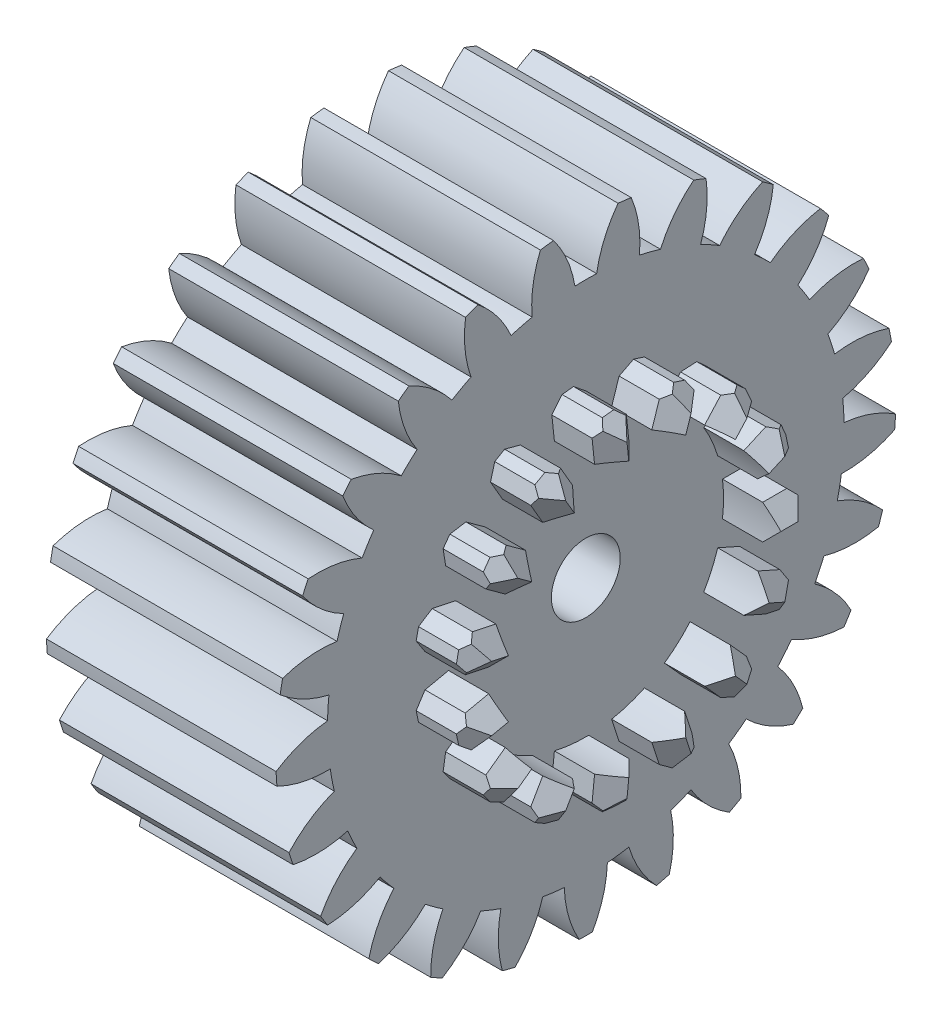
SolidWorks part; units mm, degrees
ref_plane "Plane1" through (0, 0, 0) normal (0, 0, 1) x (1, 0, 0)
ref_plane "Plane2" through (0, 0, 0) normal (0, 1, 0) x (1, 0, 0)
ref_plane "Plane3" through (0, 0, 0) normal (1, 0, 0) x (0, 0, -1)
sketch "HoldingSke" plane through (0, 0, 0) normal (0, 1, 0) x (1, 0, 0)
  line L0 (0, 0) -> (0.4532, -0.2113)
  line L1 (-15, 0) -> (100, 0) construction
  line L2 (0, 0) -> (-2.1039, 2.3779)
  line L3 (0, 0) -> (-11.863, 4.5341)
  line L4 (0, 0) -> (7.8269, 3.6497)
  line L5 (0, 0) -> (-46.8476, -17.4728)
  line L6 (0, 0) -> (-16.5793, -11.1861)
  line L7 (-2.1039, 2.3779) -> (8.6586, 51.2059)
  line L8 (-76.2, 54.61) -> (-75.2, 54.61)
  line L9 (-71.009, 38.7566) -> (-53.1078, 45.2721)
  line L10 (-76.2, 71.12) -> (104.1128, 71.12)
  line L11 (0, 0) -> (-20, 0)
  line L12 (-76.2, 101.6) -> (-76.133, 101.6)
  line L13 (24.9733, 27.94) -> (52.9518, 28.4284)
  line L14 (24.9733, 27.94) -> (24.9743, 27.94)
  line L15 (24.9733, 27.94) -> (100.4006, 29.5858)
  line L16 (-63.627, -2) -> (-12.827, -2)
  circle A0 centre (0, 0) radius 3
  circle A1 centre (0, 0) radius 22.499
  circle A2 centre (0, 0) radius 37.5
  circle A3 centre (0, 0) radius 3
  dimension "Num_teeth" = 25
  dimension "Pitch_radius" = 180.3128
  dimension "Width" = 20
  dimension "Thickness" = 20
sketch "BasProSke" plane through (0, 0, 0) normal (0, 1, 0) x (1, 0, 0)
  line L0 (-10, 0) -> (60, 0) construction
  line L1 (0, 0) -> (0, 27)
  line L2 (0, 0) -> (20, 0)
  line L3 (20, 0) -> (20, 27)
  line L4 (20, 27) -> (0, 27)
  dimension "Thickness" = 20
  dimension "Diameter" = 54
revolve "Base-Revolve" add sketch "BasProSke" angle 360 about L0
sketch "TooCutSke" plane through (0, 0, 0) normal (1, 0, 0) x (0, 0, -1)
  line L1 (0, 0) -> (0, 107) construction
  line L2 (0, 0) -> (-1.687, 24.943) construction
  line L3 (0, 0) -> (-6.2561, 49.5219) construction
  line L4 (-1.687, 24.943) -> (-3.128, 24.761) construction
  arc A0 (0.9462, 22.4791) -> (-0.9462, 22.4791) centre (0, 0) ccw
  arc A1 (2.8295, 26.8769) -> (-2.8295, 26.8769) centre (0, 0) ccw
  circle A2 centre (0, 0) radius 25 construction
  circle A3 centre (0, 0) radius 23.4923 construction
  arc A4 (-0.9462, 22.4791) -> (-2.8295, 26.8769) centre (-10.8135, 20.8556) ccw
  arc A5 (2.8295, 26.8769) -> (0.9462, 22.4791) centre (10.8135, 20.8556) ccw
extrude "ToothCut" cut sketch "TooCutSke" along normal through all
fillet "Breaks" [suppressed] radius 0.04 tangent propagation no
fillet "RootFillets" [suppressed] radius 0.501
pattern_circular "TeethCuts" count 25 every 14.4 about axis through (-10, 0, 0) along (1, 0, 0) of "ToothCut", "RootFillets", "Breaks"
sketch "HubNeaOneSke" plane through (0, 0, 0) normal (-1, 0, 0) x (0, 0, 1)
  circle A0 centre (0, 0) radius 22.499
  dimension "Diameter" = 44.998
extrude "HubNearOne" [suppressed] add sketch "HubNeaOneSke" along normal blind 30.0001
sketch "HubNeaBotSke" plane through (0, 0, 0) normal (-1, 0, 0) x (0, 0, 1)
  circle A0 centre (0, 0) radius 22.499
  dimension "Diameter" = 44.998
extrude "HubNearBoth" [suppressed] add sketch "HubNeaBotSke" along normal blind 15
ref_plane "FarPln" through (20, 0, 0) normal (1, 0, 0) x (0, 0, -1)
sketch "HubFarSke" plane through (20, 0, 0) normal (1, 0, 0) x (0, 0, -1)
  circle A0 centre (0, 0) radius 22.499
  dimension "Diameter" = 44.998
extrude "HubFar" [suppressed] add sketch "HubFarSke" along normal blind 15
sketch "BorSke" plane through (0, 0, 0) normal (1, 0, 0) x (0, 0, -1)
  circle A0 centre (0, 0) radius 3
  dimension "Diameter" = 6
extrude "Bore" cut sketch "BorSke" along normal mid plane 100.0001
sketch "KeySke" plane through (0, 0, 0) normal (1, 0, 0) x (0, 0, -1)
  line L0 (-1, 0) -> (-1, 4)
  line L1 (-1, 4) -> (1, 4)
  line L2 (1, 4) -> (1, 0)
  line L3 (0, 0) -> (0, 34) construction
  line L4 (-1, 0) -> (1, 0)
  dimension "Width" = 2
extrude "Keyway" [suppressed] cut sketch "KeySke" along normal mid plane 100.0001
pattern_circular "Keyway2" [suppressed] count 2 every 90 about axis through (-10, 0, 0) along (1, 0, 0) reverse direction yes
sketch "Sketch3" plane through (20, 0, 0) normal (1, 0, 0) x (0, 0, -1)
  line L0 (0, 0) -> (12, 0) construction
  line L1 (12, 0) -> (15, 0) construction
  line L2 (15, 0.5) -> (15, -0.5)
  line L3 (14, -1.5) -> (11.9059, -1.5)
  line L4 (14, 1.5) -> (11.9059, 1.5)
  line L5 (11.9059, 1.5) -> (11.9059, -1.5)
  line L6 (15, -0.5) -> (14, -1.5)
  line L7 (15, 0.5) -> (14, 1.5)
  line L8 (11.4867, -3.4722) -> (10.2665, -6.2129)
  line L9 (12.1795, -7.0646) -> (10.2665, -6.2129)
  line L10 (13.4998, -6.5578) -> (12.1795, -7.0646)
  line L11 (13.9066, -5.6443) -> (13.4998, -6.5578)
  line L12 (13.9066, -5.6443) -> (13.3997, -4.324)
  line L13 (13.3997, -4.324) -> (11.4867, -3.4722)
  line L14 (9.0813, -7.8441) -> (6.8519, -9.8515)
  line L15 (8.2531, -11.4077) -> (6.8519, -9.8515)
  line L16 (9.6654, -11.4817) -> (8.2531, -11.4077)
  line L17 (10.4085, -10.8126) -> (9.6654, -11.4817)
  line L18 (10.4085, -10.8126) -> (10.4825, -9.4003)
  line L19 (10.4825, -9.4003) -> (9.0813, -7.8441)
  line L20 (5.1057, -10.8596) -> (2.2525, -11.7867)
  line L21 (2.8997, -13.7783) -> (2.2525, -11.7867)
  line L22 (4.1597, -14.4204) -> (2.8997, -13.7783)
  line L23 (5.1108, -14.1113) -> (4.1597, -14.4204)
  line L24 (5.1108, -14.1113) -> (5.7528, -12.8513)
  line L25 (5.7528, -12.8513) -> (5.1057, -10.8596)
  line L26 (0.2473, -11.9975) -> (-2.7363, -11.6839)
  line L27 (-2.9552, -13.7665) -> (-2.7363, -11.6839)
  line L28 (-2.0652, -14.8656) -> (-2.9552, -13.7665)
  line L29 (-1.0707, -14.9701) -> (-2.0652, -14.8656)
  line L30 (-1.0707, -14.9701) -> (0.0284, -14.0801)
  line L31 (0.0284, -14.0801) -> (0.2473, -11.9975)
  line L32 (-4.6539, -11.0608) -> (-7.252, -9.5608)
  line L33 (-8.299, -11.3744) -> (-7.252, -9.5608)
  line L34 (-7.933, -12.7404) -> (-8.299, -11.3744)
  line L35 (-7.067, -13.2404) -> (-7.933, -12.7404)
  line L36 (-7.067, -13.2404) -> (-5.701, -12.8744)
  line L37 (-5.701, -12.8744) -> (-4.6539, -11.0608)
  line L38 (-8.7504, -8.2116) -> (-10.5137, -5.7846)
  line L39 (-12.2079, -7.0155) -> (-10.5137, -5.7846)
  line L40 (-12.4291, -8.4123) -> (-12.2079, -7.0155)
  line L41 (-11.8414, -9.2213) -> (-12.4291, -8.4123)
  line L42 (-11.8414, -9.2213) -> (-10.4446, -9.4425)
  line L43 (-10.4446, -9.4425) -> (-8.7504, -8.2116)
  line L44 (-11.3338, -3.9426) -> (-11.9576, -1.0082)
  line L45 (-14.0059, -1.4435) -> (-11.9576, -1.0082)
  line L46 (-14.7762, -2.6296) -> (-14.0059, -1.4435)
  line L47 (-14.5683, -3.6077) -> (-14.7762, -2.6296)
  line L48 (-14.5683, -3.6077) -> (-13.3822, -4.378)
  line L49 (-13.3822, -4.378) -> (-11.3338, -3.9426)
  line L50 (-11.9576, 1.0082) -> (-11.3338, 3.9426)
  line L51 (-13.3822, 4.378) -> (-11.3338, 3.9426)
  line L52 (-14.5683, 3.6077) -> (-13.3822, 4.378)
  line L53 (-14.7762, 2.6296) -> (-14.5683, 3.6077)
  line L54 (-14.7762, 2.6296) -> (-14.0059, 1.4435)
  line L55 (-14.0059, 1.4435) -> (-11.9576, 1.0082)
  line L56 (-10.5137, 5.7846) -> (-8.7504, 8.2116)
  line L57 (-10.4446, 9.4425) -> (-8.7504, 8.2116)
  line L58 (-11.8414, 9.2213) -> (-10.4446, 9.4425)
  line L59 (-12.4291, 8.4123) -> (-11.8414, 9.2213)
  line L60 (-12.4291, 8.4123) -> (-12.2079, 7.0155)
  line L61 (-12.2079, 7.0155) -> (-10.5137, 5.7846)
  line L62 (-7.252, 9.5608) -> (-4.6539, 11.0608)
  line L63 (-5.701, 12.8744) -> (-4.6539, 11.0608)
  line L64 (-7.067, 13.2404) -> (-5.701, 12.8744)
  line L65 (-7.933, 12.7404) -> (-7.067, 13.2404)
  line L66 (-7.933, 12.7404) -> (-8.299, 11.3744)
  line L67 (-8.299, 11.3744) -> (-7.252, 9.5608)
  line L68 (-2.7363, 11.6839) -> (0.2473, 11.9975)
  line L69 (0.0284, 14.0801) -> (0.2473, 11.9975)
  line L70 (-1.0707, 14.9701) -> (0.0284, 14.0801)
  line L71 (-2.0652, 14.8656) -> (-1.0707, 14.9701)
  line L72 (-2.0652, 14.8656) -> (-2.9552, 13.7665)
  line L73 (-2.9552, 13.7665) -> (-2.7363, 11.6839)
  line L74 (2.2525, 11.7867) -> (5.1057, 10.8596)
  line L75 (5.7528, 12.8513) -> (5.1057, 10.8596)
  line L76 (5.1108, 14.1113) -> (5.7528, 12.8513)
  line L77 (4.1597, 14.4204) -> (5.1108, 14.1113)
  line L78 (4.1597, 14.4204) -> (2.8997, 13.7783)
  line L79 (2.8997, 13.7783) -> (2.2525, 11.7867)
  line L80 (6.8519, 9.8515) -> (9.0813, 7.8441)
  line L81 (10.4825, 9.4003) -> (9.0813, 7.8441)
  line L82 (10.4085, 10.8126) -> (10.4825, 9.4003)
  line L83 (9.6654, 11.4817) -> (10.4085, 10.8126)
  line L84 (9.6654, 11.4817) -> (8.2531, 11.4077)
  line L85 (8.2531, 11.4077) -> (6.8519, 9.8515)
  line L86 (10.2665, 6.2129) -> (11.4867, 3.4722)
  line L87 (13.3997, 4.324) -> (11.4867, 3.4722)
  line L88 (13.9066, 5.6443) -> (13.3997, 4.324)
  line L89 (13.4998, 6.5578) -> (13.9066, 5.6443)
  line L90 (13.4998, 6.5578) -> (12.1795, 7.0646)
  line L91 (12.1795, 7.0646) -> (10.2665, 6.2129)
  circle A0 centre (0, 0) radius 12
  point P6 (15, -1.5)
  point P7 (15, 1.5)
  point P8 (15, 0)
  dimension "D1" = 15
extrude "Boss-Extrude2" add sketch "Sketch3" along normal blind 5 contours A0 L9 L10 L11 L12 L13 | A0 L15 L16 L17 L18 L19 | A0 L21 L22 L23 L24 L25 | A0 L27 L28 L29 L30 L31 | A0 L33 L34 L35 L36 L37 | A0 L39 L40 L41 L42 L43 | A0 L45 L46 L47 L48 L49 | A0 L51 L52 L53 L54 L55 | A0 L57 L58 L59 L60 L61 | A0 L63 L64 L65 L66 L67 | A0 L69 L70 L71 L72 L73 | A0 L75 L76 L77 L78 L79 | A0 L81 L82 L83 L84 L85 | A0 L87 L88 L89 L90 L91 | A0 L3 L6 L2 L7 L4 region at (20, 0, -13.3381) region at (20, 5.4251, -12.185) region at (20, -5.4251, -12.185) region at (20, 9.9122, -8.9249) region at (20, -9.9122, -8.9249) region at (20, 12.6853, -4.1217) region at (20, -12.6853, -4.1217) region at (20, 13.265, 1.3942) region at (20, -13.265, 1.3942) region at (20, 11.5511, 6.6691) region at (20, -11.5511, 6.6691) region at (20, 7.8399, 10.7908) region at (20, -7.8399, 10.7908) region at (20, 2.7732, 13.0466) region at (20, -2.7732, 13.0466)
chamfer "Chamfer1" distance 1.5 angle 45 45 edges at (25, 8.8168, 12.1353) (25, 6.4, 11.3608) (25, 8.8271, 9.5975) (25, 10.4676, 7.7755) (25, 12.9904, 7.5) (25, 11.9676, 5.1774) (25, 12.7252, 2.8457) (25, 14.9178, 1.5679) (25, 13.0388, -0.1378) (25, 12.7825, -2.5761) (25, 14.2658, -4.6353) (25, 11.8555, -5.4293) (25, 4.1603, 12.358) (25, 3.1187, 14.6722) (25, 1.2258, 12.9818) (25, -1.2258, 12.9818) (25, -4.1603, 12.358) (25, -3.1187, 14.6722) (25, -8.8168, 12.1353) (25, -6.4, 11.3608) (25, -8.8271, 9.5975) (25, -12.9904, 7.5) (25, -11.9676, 5.1774) (25, -10.4676, 7.7755) (25, -14.9178, 1.5679) (25, -14.2658, -4.6353) (25, -11.1472, -10.037) (25, -12.7252, 2.8457) (25, -13.0388, -0.1378) (25, -11.8555, -5.4293) (25, -12.7825, -2.5761) (25, -8.6222, -9.7819) (25, -10.6296, -7.5525) (25, -3.8981, -12.4432) (25, -6.101, -13.7032) (25, -6.6388, -11.223) (25, 1.5, -12.9529) (25, 0, -15) (25, -1.5, -12.9529) (25, 6.6388, -11.223) (25, 6.101, -13.7032) (25, 3.8981, -12.4432) (25, 10.6296, -7.5525) (25, 11.1472, -10.037) (25, 8.6222, -9.7819)
equation "' \"Module@HoldingSke\" = 6.35"
equation "' \"Num_teeth@HoldingSke\" = 12"
equation "' \"Ap@HoldingSke\" =  20"
equation "' \"Ap@HoldingSke\" = 20"
equation "' \"Width@HoldingSke\" = 0.5 * 25.4"
equation "' \"Hub_dia@HoldingSke\"= 1 * 25.4"
equation "' \"Hub_dia@HoldingSke\" = 1 * 25.4"
equation "' \"Overall_len@HoldingSke\" = 1.0 * 25.4"
equation "' \"Bore@HoldingSke\" = 0.75 * 25.4"
equation "' \"T_dim@HoldingSke\" = 0.1 * 25.4"
equation "' \"Width@KeySke\" = 0.25 * 25.4"
equation "' \"Show_teeth@HoldingSke\" = 13"
equation "' \"Backlash@HoldingSke\" = 0.009 * 25.4"
equation "' \"Addendum_fac@HoldingSke\" = 1.0"
equation "' \"Dedendum_fac@HoldingSke\" = 1.25"
equation "' \"Dedendum_add@HoldingSke\" = 0.00005 * 25.4"
equation "' \"Clearance_fac@HoldingSke\" = 0.25"
equation "\"Pitch@HoldingSke\" = 1 / \"Module@HoldingSke\""
equation "\"Overcut_dia@TooCutSke\" = (\"Num_teeth@HoldingSke\" + 2 * \"Addendum_fac@HoldingSke\") / \"Pitch@HoldingSke\" + 0.002 * 25.4"
equation "\"Pitch_dia@TooCutSke\" = \"Num_teeth@HoldingSke\" / \"Pitch@HoldingSke\""
equation "\"Base_dia@TooCutSke\" = \"Num_teeth@HoldingSke\" / \"Pitch@HoldingSke\" * cos((\"Ap@HoldingSke\"  * 3.14159265 / 180))"
equation "\"Root_dia@TooCutSke\" = (\"Num_teeth@HoldingSke\" + 2) / \"Pitch@HoldingSke\" - 2 * (\"Addendum_fac@HoldingSke\" + \"Dedendum_fac@HoldingSke\") / \"Pitch@HoldingSke\" - \"Dedendum_add@HoldingSke\" * 2"
equation "\"Half_ang@TooCutSke\" = 180 / \"Num_teeth@HoldingSke\""
equation "\"Half_CT@TooCutSke\" = \"Num_teeth@HoldingSke\" / \"Pitch@HoldingSke\" * sin((3.14159265 / 2 / \"Num_teeth@HoldingSke\")) / 2 - 7 * \"Backlash@HoldingSke\" / 4"
equation "\"Flank_rad@TooCutSke\" = \"Num_teeth@HoldingSke\" / \"Pitch@HoldingSke\" / 5"
equation "\"Radius@RootFillets\" = \"Clearance_fac@HoldingSke\" / \"Pitch@HoldingSke\" + \"Dedendum_add@HoldingSke\""
equation "\"Break_rad@Breaks\" = 0.02 / \"Pitch@HoldingSke\""
equation "\"Thickness@HoldingSke\" = \"Width@HoldingSke\""
equation "\"OAL@HoldingSke\" = \"Thickness@HoldingSke\""
equation "\"MHD@HoldingSke\" = (\"Num_teeth@HoldingSke\" + 2) / \"Pitch@HoldingSke\" - 2 * (\"Addendum_fac@HoldingSke\" + \"Dedendum_fac@HoldingSke\")  / \"Pitch@HoldingSke\" - \"Dedendum_add@HoldingSke\" * 2"
equation "\"MBD@HoldingSke\" = (\"Num_teeth@HoldingSke\" + 2) / \"Pitch@HoldingSke\" - 2 * (\"Addendum_fac@HoldingSke\" + \"Dedendum_fac@HoldingSke\")  / \"Pitch@HoldingSke\" - \"Dedendum_add@HoldingSke\" * 2 - 0.002 * 25.4"
equation "\"MHD@HoldingSke\" = ((sgn( \"MHD@HoldingSke\" - \"Hub_dia@HoldingSke\" )-1)*( \"MHD@HoldingSke\" - \"Hub_dia@HoldingSke\" ))/-2+ \"Hub_dia@HoldingSke\""
equation "\"MBD@HoldingSke\" = ((sgn( \"MBD@HoldingSke\" - \"Bore@HoldingSke\" )-1)*( \"MBD@HoldingSke\" - \"Bore@HoldingSke\" ))/-2+ \"Bore@HoldingSke\""
equation "\"OAL@HoldingSke\" = ((sgn( \"OAL@HoldingSke\" - \"Overall_len@HoldingSke\" )+1)*( \"OAL@HoldingSke\" - \"Overall_len@HoldingSke\" ))/2 + \"Overall_len@HoldingSke\" + 0.000002 * 25.4"
equation "\"Num_teeth@TeethCuts\" = int( \"Show_teeth@HoldingSke\" ) + 1"
equation "\"Num_teeth@TeethCuts\" = ((sgn( \"Num_teeth@TeethCuts\" - \"Num_teeth@HoldingSke\" )-1)*( \"Num_teeth@TeethCuts\" - \"Num_teeth@HoldingSke\" ))/-2+ \"Num_teeth@HoldingSke\""
equation "\"Num_teeth@TeethCuts\" = ((sgn( \"Num_teeth@TeethCuts\" - 2.0)+1)*( \"Num_teeth@TeethCuts\" - 2.0))/2 +2.0"
equation "\"Angle@TeethCuts\" = 360.0 / \"Num_teeth@HoldingSke\""
equation "\"Diameter@BasProSke\" = (\"Num_teeth@HoldingSke\" + 2 * \"Addendum_fac@HoldingSke\") / \"Pitch@HoldingSke\""
equation "\"Thickness@BasProSke\"  = \"Thickness@HoldingSke\""
equation "' \"Fillet_rad@BasProSke\" =  \"Thickness@HoldingSke\" * 0.05"
equation "' \"Fillet_rad@BasProSke\" = \"Thickness@HoldingSke\" * 0.05"
equation "\"MHD@HoldingSke\" = ((sgn( \"MHD@HoldingSke\" - \"Root_dia@TooCutSke\" )-1)*( \"MHD@HoldingSke\" - \"Root_dia@TooCutSke\" ))/-2+ \"Root_dia@TooCutSke\""
equation "\"Diameter@HubNeaOneSke\" = \"MHD@HoldingSke\""
equation "\"Length@HubNearOne\" = \"OAL@HoldingSke\" - \"Thickness@BasProSke\""
equation "\"Diameter@HubNeaBotSke\" = \"MHD@HoldingSke\""
equation "\"Length@HubNearBoth\" = ( \"OAL@HoldingSke\" - \"Thickness@BasProSke\" ) / 2.0"
equation "\"Thickness@FarPln\" = \"Thickness@BasProSke\""
equation "\"Diameter@HubFarSke\" = \"MHD@HoldingSke\""
equation "\"Length@HubFar\" = ( \"OAL@HoldingSke\" - \"Thickness@BasProSke\" ) / 2.0"
equation "\"Diameter@BorSke\" = \"MBD@HoldingSke\""
equation "\"D1@Bore\" = \"OAL@HoldingSke\" * 2.0"
equation "\"D1@Keyway\" = \"OAL@HoldingSke\" * 2.0"
equation "\"Offset@KeySke\" = \"T_dim@HoldingSke\" + \"MBD@HoldingSke\" / 2.0"
